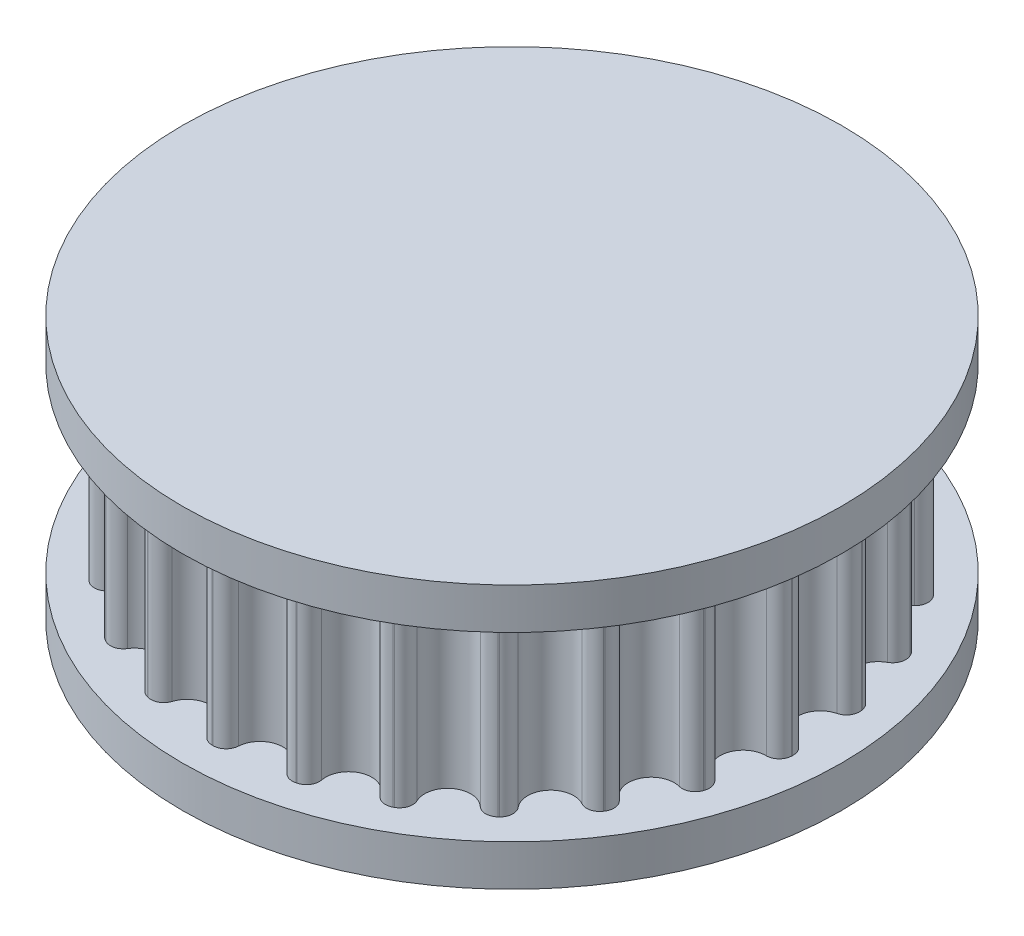
SolidWorks part; units mm, degrees
ref_plane "Front Plane" through (0, 0, 0) normal (0, 0, 1) x (1, 0, 0)
ref_plane "Top Plane" through (0, 0, 0) normal (0, 1, 0) x (1, 0, 0)
ref_plane "Right Plane" through (0, 0, 0) normal (1, 0, 0) x (0, 0, -1)
sketch "Sketch1" plane through (0, 0, 0) normal (0, 1, 0) x (1, 0, 0)
  line L0 (0, 0) -> (0, 11.555) construction
  line L1 (0, 0) -> (2.7915, 10.8723) construction
  circle A0 centre (0, 0) radius 11.555 construction
  circle A1 centre (0, 0) radius 10.335 construction
  circle A2 centre (0, 11.225) radius 0.89 construction
  circle A5 centre (2.7915, 10.8723) radius 0.89 construction
  arc A6 (0, 10.335) -> (0.8749, 11.0618) centre (0, 11.225) ccw
  arc A7 (0.8749, 11.0618) -> (1.4283, 11.4664) centre (1.3665, 10.9702) cw
  arc A8 (1.4682, 11.4613) -> (1.9035, 10.9319) centre (1.4047, 10.9654) cw
  arc A9 (2.5702, 10.0103) -> (1.9035, 10.9319) centre (2.7915, 10.8723) cw
  arc A10 (1.4283, 11.4664) -> (1.4682, 11.4613) centre (0, 0) cw
  arc A11 (0, 10.335) -> (2.5702, 10.0103) centre (0, 0) ccw
  dimension "D1" = 23.1099
  dimension "D3" = 1.78
  dimension "D4" = 0.5
  dimension "D2" = 1.22
  dimension "D5" = 14.4
extrude "Boss-Extrude1" add sketch "Sketch1" along normal mid plane 7.112 contours A6 A11 A9 A8 A7 region at (0.0057, 0, -0.0455)
ref_axis "Axis1" through (0, 3.3, 0) along (0, -1, 0)
pattern_circular "CirPattern1" count 25 over 360 about axis through (0, 3.3, 0) along (0, -1, 0) of "Boss-Extrude1"
sketch "Sketch2" plane through (0, 0, 0) normal (1, 0, 0) x (0, 0, -1)
  line L10 (0, 3.5) -> (12.7297, 3.5) construction
  line L11 (0, 3.5) -> (0, 5.0875) construction
  line L12 (0, 5.0875) -> (12.7297, 5.0875) construction
  line L15 (12.7297, 3.5) -> (12.7297, 5.0875) construction
  line L20 (0, 3.3) -> (0, -3.3) construction
  line L22 (12.7297, 5.0875) -> (0, 5.0875)
  line L23 (12.7297, 5.0875) -> (12.7297, 3.5)
  line L24 (12.7297, 3.5) -> (0, 3.5)
  line L25 (0, 5.0875) -> (0, 3.5)
  dimension "D1" = 1.5875
  dimension "D2" = 12.7297
  dimension "D3" = 3.5
revolve "Revolve3" add sketch "Sketch2" angle 360 about axis through (0, 3.3, 0) along (0, -1, 0) region at (0, 4.2937, -6.3649)
mirror "Mirror1" about plane through (0, 0, 0) normal (0, 1, 0) of "Revolve3"
equation "\"TEETH_NUM\" = 25"
equation "\"TOOTH_PITCH\"= 3mm"
equation "\"PITCH_LINE_OFFSET\"= .015in"
equation "\"DIAMETER_PER_GROOVE\"= \"OUTSIDE_DIAMETER\" / \"TEETH_NUM\" * 1in"
equation "\"PITCH_DIAMETER\"= ( ( \"TEETH_NUM\" * 3 - 1.31 ) / 3.1415 + .415 ) * 1mm"
equation "\"OUTSIDE_DIAMETER\"= \"PITCH_DIAMETER\" - \"PITCH_LINE_OFFSET\" * 2"
equation "\"D1@Sketch1\"=\"OUTSIDE_DIAMETER\""
equation "\"TOOTH_HEIGHT\"= 1.22mm"
equation "\"D2@Sketch1\"=\"TOOTH_HEIGHT\""
equation "\"TOOTH_DIAMETER\"= 1.78mm"
equation "\"INTERNAL_RADIUS\"= .5mm"
equation "\"D3@Sketch1\"=\"TOOTH_DIAMETER\""
equation "\"D5@Sketch1\"=360 / \"TEETH_NUM\""
equation "\"D4@Sketch1\"=\"INTERNAL_RADIUS\""
equation "\"D1@CirPattern1\"=\"TEETH_NUM\""
equation "\"BELT_GAP\"= 7mm"
equation "\"D2@Sketch2\"=\"PITCH_DIAMETER\"/2+1/32"
equation "\"D3@Sketch2\"=\"BELT_GAP\"/2"
